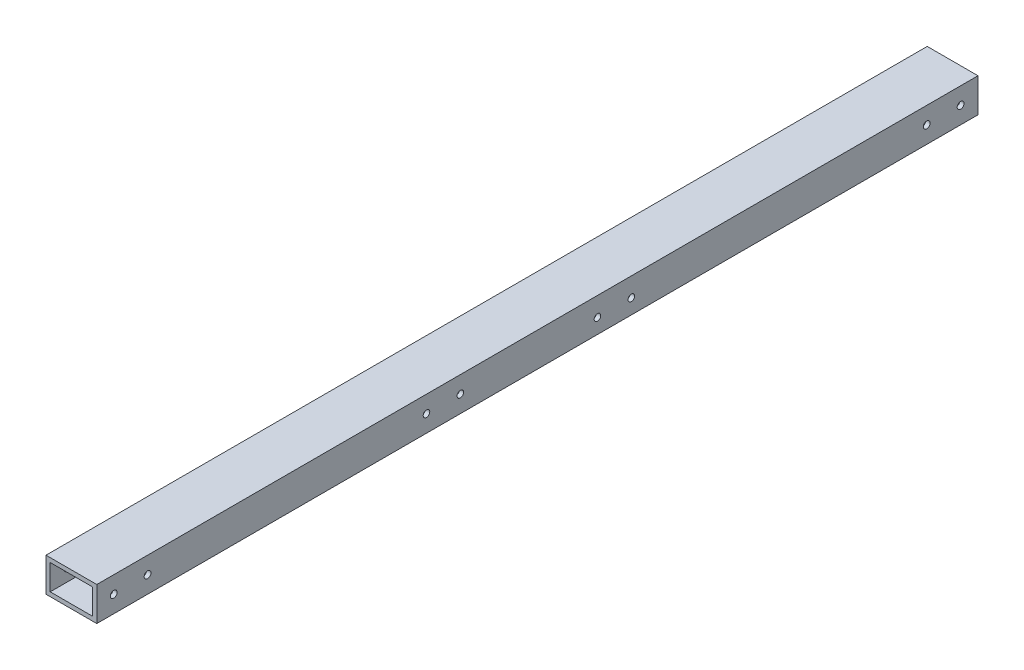
SolidWorks part; units mm, degrees
ref_plane "Front Plane" through (0, 0, 0) normal (0, 0, 1) x (1, 0, 0)
ref_plane "Top Plane" through (0, 0, 0) normal (0, 1, 0) x (1, 0, 0)
ref_plane "Right Plane" through (0, 0, 0) normal (1, 0, 0) x (0, 0, -1)
sketch "Sketch1" plane through (0, 0, 0) normal (0, 0, 1) x (1, 0, 0)
  line L0 (-15.875, 9.525) -> (15.875, 9.525)
  line L2 (-19.05, 12.7) -> (19.05, 12.7)
  line L3 (-19.05, 12.7) -> (-19.05, -12.7)
  line L4 (-19.05, -12.7) -> (19.05, -12.7)
  line L5 (19.05, 12.7) -> (19.05, -12.7)
  line L10 (15.875, 9.525) -> (15.875, -9.525)
  line L11 (-15.875, -9.525) -> (15.875, -9.525)
  line L12 (-15.875, 9.525) -> (-15.875, -9.525)
  point P12 (0, 12.7)
  point P14 (19.05, 0)
  dimension "Wall Thickness" = 3.175
  dimension "Outside Width" = 38.1
  dimension "Outside Height" = 25.4
  dimension "Inside Height" = 19.05
  dimension "Inside Width" = 31.75
sketch "Sketch2" plane through (0, 0, 0) normal (1, 0, 0) x (0, 0, -1)
  line L0 (330.5556, 0) -> (-330.5556, 0)
  point P4 (0, 0)
  point P7 (-330.5556, 0)
  point P10 (330.5556, 0)
  dimension "Length" = 661.1112
sketch "Sketch3" plane through (0, 0, 0) normal (0, 0, 1) x (1, 0, 0)
  line L21 (19.05, 12.7) -> (-19.05, 12.7)
  line L22 (19.05, -12.7) -> (19.05, 12.7)
  line L23 (-19.05, -12.7) -> (19.05, -12.7)
  line L24 (-19.05, 12.7) -> (-19.05, -12.7)
  line L25 (19.05, 12.7) -> (-19.05, 12.7)
  line L26 (19.05, -12.7) -> (19.05, 12.7)
  line L27 (-19.05, -12.7) -> (19.05, -12.7)
  line L28 (-19.05, 12.7) -> (-19.05, -12.7)
  line L29 (15.875, 9.525) -> (-15.875, 9.525)
  line L30 (15.875, -9.525) -> (15.875, 9.525)
  line L31 (-15.875, -9.525) -> (15.875, -9.525)
  line L32 (-15.875, 9.525) -> (-15.875, -9.525)
  line L33 (15.875, 9.525) -> (-15.875, 9.525)
  line L34 (15.875, -9.525) -> (15.875, 9.525)
  line L35 (-15.875, -9.525) -> (15.875, -9.525)
  line L36 (-15.875, 9.525) -> (-15.875, -9.525)
  dimension "D1" = 0
  dimension "D2" = 0
extrude "Boss-Extrude1" add sketch "Sketch3" along normal up to vertex (330.5556 mm away) and the other way up to vertex (330.5556 mm away) up to point (0, 0, 330.5556) other way up to point (0, 0, -330.5556)
sketch "Drawing Reference" plane through (0, 0, 0) normal (1, 0, 0) x (0, 0, -1)
  line L0 (-330.5556, 0) -> (330.5556, 0) construction
  line L1 (0, -12.7) -> (0, 12.7) construction
  line L2 (-330.5556, -12.7) -> (330.5556, -12.7) construction
  line L5 (-330.5556, 12.7) -> (330.5556, 12.7) construction
  point P7 (-303.1236, 0)
  point P8 (303.1236, 0)
  dimension "D1" = 27.432
sketch "Sketch4" plane through (-19.05, 0, 0) normal (-1, 0, 0) x (0, 0, 1)
  line L0 (-330.5556, 0) -> (-317.5, 0)
  line L1 (-330.5556, 12.7) -> (-330.5556, -12.7) construction
  line L2 (-317.5, 0) -> (-292.1, 0)
  line L3 (330.5556, 12.7) -> (330.5556, -12.7) construction
  line L4 (330.5556, 0) -> (317.8556, 0)
  line L5 (317.8556, 0) -> (292.4556, 0)
  point P11 (-317.5, 0)
  point P13 (-292.1, 0)
  point P14 (317.8556, 0)
  point P15 (292.4556, 0)
hole_wizard "#10 Clearance Hole2" positions "Sketch11" profile "Sketch12" hole size "#10" standard "ANSI Inch" end condition through all
sketch "Sketch11" plane through (-19.05, 0, 0) normal (-1, 0, 0) x (0, 0, 1)
  point P0 (-317.5, 0)
  point P3 (-292.1, 0)
  point P6 (292.4556, 0)
  point P9 (317.8556, 0)
sketch "Sketch12" plane through (-19.05, 0, -317.5) normal (0, 1, 0) x (0, 0, 1)
  line L0 (0, 0) -> (0, 38.1)
  line L1 (0, 38.1) -> (2.5527, 38.1)
  line L2 (2.5527, 38.1) -> (2.5527, 0)
  line L5 (2.5527, 0) -> (0, 0)
  line L11 (0, -6.35) -> (0, 107.95) construction
  dimension "Thru Hole Dia." = 5.1054
  dimension "Thru Hole Depth" = 38.1
sketch "Sketch13" plane through (19.05, 0, 0) normal (1, 0, 0) x (0, 0, -1)
  line L0 (70.4596, -1.5875) -> (45.0596, -1.5875)
  line L1 (70.4596, -1.5875) -> (70.4596, -12.7)
  line L2 (-330.5556, -12.7) -> (330.5556, -12.7) construction
hole_wizard "#10 (0.1935) Diameter Hole1" positions "Sketch14" profile "Sketch16" hole size "#10" standard "ANSI Inch" end condition through all
sketch "Sketch14" plane through (19.05, 0, 0) normal (1, 0, 0) x (0, 0, -1)
  point P3 (70.4596, -1.5875)
  point P7 (45.0596, -1.5875)
sketch "Sketch16" plane through (19.05, -1.5875, -70.4596) normal (0, 1, 0) x (0, 0, -1)
  line L0 (0, 0) -> (0, 38.1)
  line L1 (0, 38.1) -> (2.4574, 38.1)
  line L2 (2.4574, 38.1) -> (2.4574, 0)
  line L5 (2.4574, 0) -> (0, 0)
  line L11 (0, -6.35) -> (0, 107.95) construction
  dimension "Thru Hole Dia." = 4.9149
  dimension "Thru Hole Depth" = 38.1
sketch "Sketch17" plane through (19.05, 0, 0) normal (1, 0, 0) x (0, 0, -1)
  point P0 (-83.2104, 0)
  point P1 (-57.8104, 0)
hole_wizard "#10 (0.1935) Diameter Hole2" positions "Sketch18" profile "Sketch19" hole size "#10" standard "ANSI Inch" end condition through all
sketch "Sketch18" plane through (19.05, 0, 0) normal (1, 0, 0) x (0, 0, -1)
  point P0 (-83.2104, 0)
  point P3 (-57.8104, 0)
sketch "Sketch19" plane through (19.05, 0, 83.2104) normal (0, 1, 0) x (0, 0, -1)
  line L0 (0, 0) -> (0, 38.1)
  line L1 (0, 38.1) -> (2.4574, 38.1)
  line L2 (2.4574, 38.1) -> (2.4574, 0)
  line L5 (2.4574, 0) -> (0, 0)
  line L11 (0, -6.35) -> (0, 107.95) construction
  dimension "Thru Hole Dia." = 4.9149
  dimension "Thru Hole Depth" = 38.1
equation "\"D1@Drawing Reference\"=\"Outside Width@Sketch1\" * 0.72"
